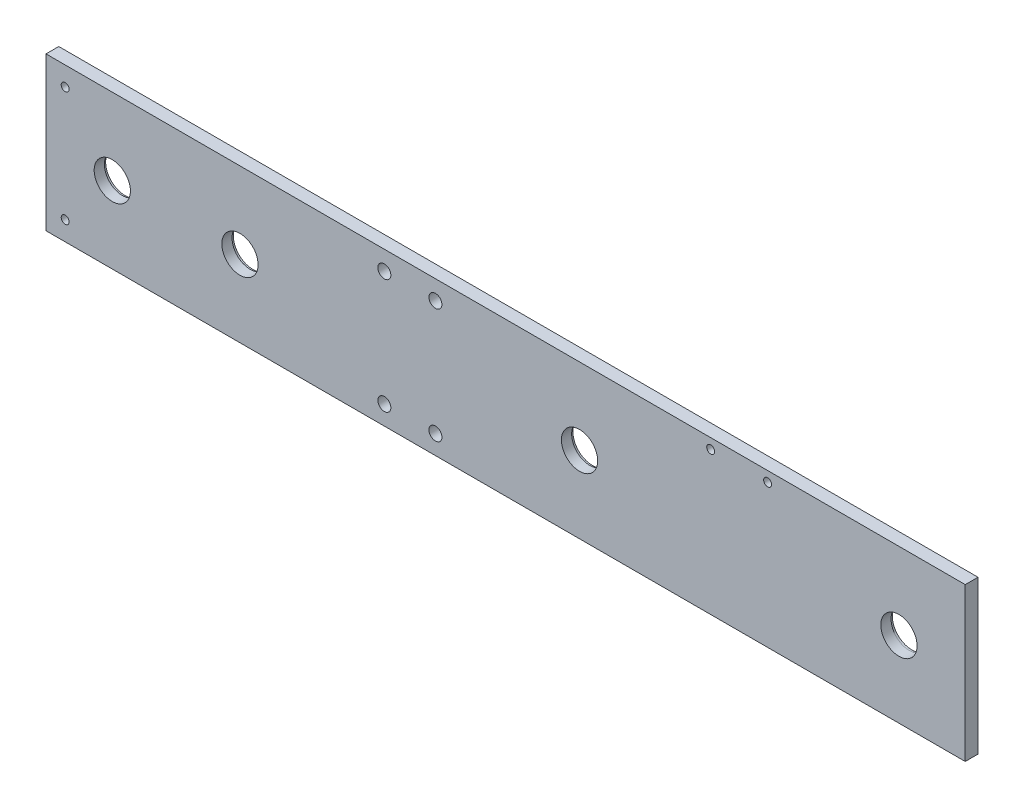
SolidWorks part; units mm, degrees
note: The reader was unsure of these and kept them because the rebuilt part matched: shared geometry of "Sketch2<3>".
ref_plane "Front Plane" through (0, 0, 0) normal (0, 0, 1) x (1, 0, 0)
ref_plane "Top Plane" through (0, 0, 0) normal (0, 1, 0) x (1, 0, 0)
ref_plane "Right Plane" through (0, 0, 0) normal (1, 0, 0) x (0, 0, -1)
sketch "Sketch1" plane through (0, 0, 0) normal (0, 0, 1) x (1, 0, 0)
  line L4 (-25.9587, 30) -> (-25.9587, -30)
  line L5 (334.0413, 30) -> (-25.9587, 30)
  line L6 (334.0413, -30) -> (334.0413, 30)
  line L7 (-25.9587, -30) -> (334.0413, -30)
  line L8 (-25.9587, 30) -> (-25.9587, -30)
  line L9 (334.0413, 30) -> (-25.9587, 30)
  line L10 (334.0413, -30) -> (334.0413, 30)
  line L11 (-25.9587, -30) -> (334.0413, -30)
  circle A0 centre (308.0826, -0.2) radius 7.1 construction
  circle A1 centre (308.0826, -0.2) radius 7.1
  circle A5 centre (0, 0) radius 7.1 construction
  circle A9 centre (-18.4514, 22.4927) radius 1.55
  circle A10 centre (0, 0) radius 7.1
  circle A11 centre (-18.4514, -22.4927) radius 1.55
  circle A12 centre (50, 0) radius 7.1
  circle A13 centre (183, 0) radius 7.1
  circle A15 centre (106.5486, -22.4927) radius 2.55
  circle A16 centre (106.5486, 22.4927) radius 2.55
  circle A18 centre (-18.4514, -22.4927) radius 1.55 construction
  circle A19 centre (-18.4514, 22.4927) radius 1.55 construction
  dimension "D2" = 14.2
  dimension "D3" = 14.2
  dimension "D4" = 125
  dimension "D5" = 5.1
  dimension "D6" = 5.1
  dimension "D7" = 3.1
  dimension "D8" = 3.1
  dimension "D1" = 0
extrude "Boss-Extrude1" add sketch "Sketch1" against normal blind 4
sketch "Sketch2" plane through (0, 0, -4) normal (0, 0, -1) x (-1, 0, 0)
  circle A0 centre (-308.0826, 0) radius 7.6 construction
  circle A1 centre (0, 0) radius 7.6 construction
  circle A2 centre (-308.0826, 0) radius 7.6
  circle A3 centre (0, 0) radius 7.6
  circle A4 centre (-50, 0) radius 7.6
  circle A5 centre (-183, 0) radius 7.6
  circle A6 centre (-106.5486, 22.4927) radius 2.55 construction
  circle A7 centre (-106.5486, -22.4927) radius 2.55 construction
  circle A8 centre (-106.5486, 22.4927) radius 2.55 construction
  circle A9 centre (-106.5486, -22.4927) radius 2.55 construction
  circle A10 centre (-126.5486, 22.4927) radius 2.55
  circle A11 centre (-126.5486, -22.4927) radius 2.55
  circle A12 centre (-256.65, 26) radius 1.55 construction
  circle A13 centre (-234.35, 26) radius 1.55 construction
  circle A14 centre (-256.65, 26) radius 1.55
  circle A15 centre (-234.35, 26) radius 1.55
  circle A16 centre (-50, 0) radius 7.1 construction
  dimension "D1" = 15.2
  dimension "D2" = 15.2
  dimension "D3" = 2
extrude "Boss-Extrude2" add sketch "Sketch2" along normal blind 1
extrude "Cut-Extrude1" cut sketch "Sketch2<3>" against normal blind 4 contours A11 | A10 | A14 | A15
sketch "Sketch2<3>" plane through (0, 0, -4) normal (0, 0, -1) x (-1, 0, 0) same geometry as "Sketch2"
